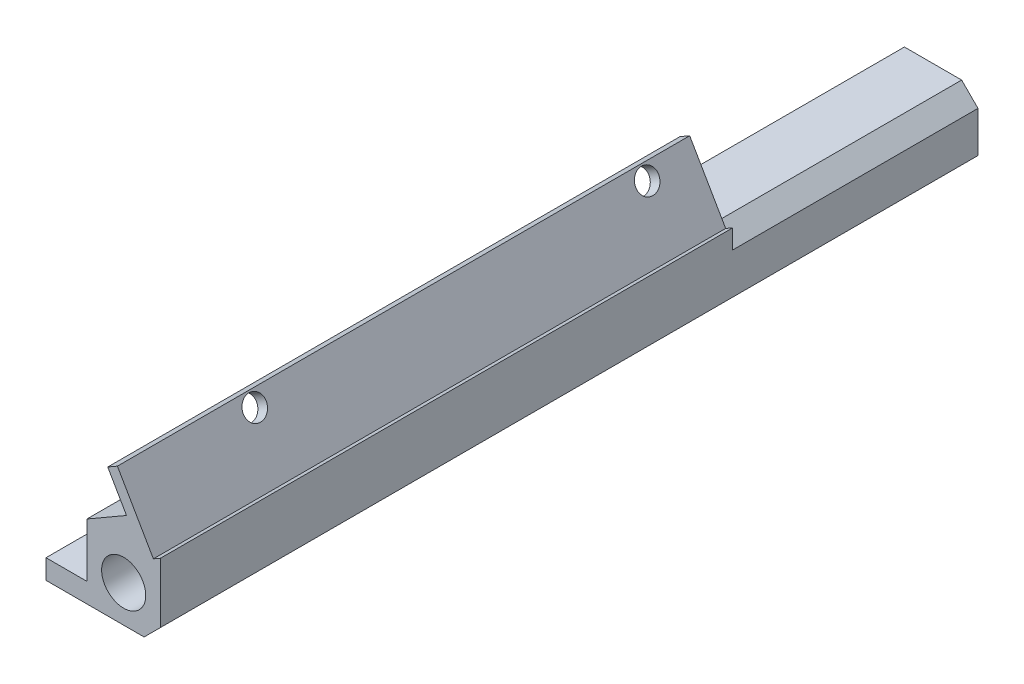
SolidWorks part; units mm, degrees
ref_plane "Front Plane" through (0, 0, 0) normal (0, 0, 1) x (1, 0, 0)
ref_plane "Top Plane" through (0, 0, 0) normal (0, 1, 0) x (1, 0, 0)
ref_plane "Right Plane" through (0, 0, 0) normal (1, 0, 0) x (0, 0, -1)
sketch "Sketch1" plane through (0, 0, 0) normal (0, 1, 0) x (1, 0, 0)
  line L1 (0, 0) -> (77.47, 0)
  line L2 (0, 0) -> (0, 127)
  line L3 (0, 127) -> (77.47, 127)
  line L4 (77.47, 0) -> (77.47, 127)
  dimension "D1" = 77.47
  dimension "D2" = 127
extrude "Boss-Extrude1" add sketch "Sketch1" along normal blind 11.43
sketch "Sketch2" plane through (0, 0, 0) normal (0, 0, 1) x (1, 0, 0)
  line L0 (5.715, 5.715) -> (71.755, 5.715) construction
  line L1 (38.735, 11.43) -> (38.735, 0) construction
  line L2 (0, 11.43) -> (77.47, 11.43) construction
  line L3 (0, 0) -> (77.47, 0) construction
  circle A0 centre (5.715, 5.715) radius 3.429
  circle A1 centre (71.755, 5.715) radius 3.429
  point P10 (38.735, 5.715)
  dimension "D1" = 6.858
  dimension "D2" = 66.04
extrude "Cut-Extrude1" cut sketch "Sketch2" against normal through all
sketch "Sketch3" plane through (0, 11.43, 0) normal (0, 1, 0) x (1, 0, 0)
  line L0 (11.43, 127) -> (11.43, 88.9)
  line L1 (77.47, 127) -> (0, 127) construction
  line L2 (11.43, 127) -> (66.04, 127)
  line L3 (66.04, 127) -> (66.04, 88.9)
  line L4 (53.34, 76.2) -> (24.13, 76.2)
  line L5 (0, 127) -> (0, 0) construction
  arc A0 (66.04, 88.9) -> (53.34, 76.2) centre (53.34, 88.9) cw
  arc A1 (24.13, 76.2) -> (11.43, 88.9) centre (24.13, 88.9) cw
  point P10 (38.735, 127)
  dimension "D1" = 12.7
  dimension "D2" = 11.43
  dimension "D3" = 50.8
extrude "Cut-Extrude2" cut sketch "Sketch3" against normal through all
sketch "Sketch4" plane through (0, 0, -127) normal (0, 0, -1) x (-1, 0, 0)
  line L0 (-11.43, 0) -> (-11.43, 11.43) construction
  line L1 (-66.04, 11.43) -> (-11.43, 11.43)
  line L2 (-66.04, 11.43) -> (-66.04, 5.08)
  line L3 (-66.04, 5.08) -> (-11.43, 5.08)
  line L4 (-11.43, 11.43) -> (-11.43, 5.08)
  line L5 (-11.43, 0) -> (0, 0) construction
  dimension "D1" = 5.08
extrude "Cut-Extrude3" cut sketch "Sketch4" against normal through all
chamfer "Chamfer1" distance 2.54 angle 45 4 edges at (0, 0, -63.5) (0, 11.43, -63.5) (77.47, 0, -63.5) (77.47, 11.43, -63.5)
sketch "Sketch5" plane through (0, 11.43, 0) normal (0, 1, 0) x (1, 0, 0)
  line L0 (66.04, 76.2) -> (0, 76.2)
  line L1 (66.04, 0) -> (66.04, 88.9) construction
  line L2 (0, 0) -> (0, 127) construction
  line L3 (0, 76.2) -> (0, 127)
  line L4 (0, 127) -> (66.04, 127)
  line L5 (66.04, 127) -> (66.04, 76.2)
  line L6 (24.13, 76.2) -> (53.34, 76.2) construction
extrude "Cut-Extrude4" cut sketch "Sketch5" against normal through all
sketch "Sketch6" plane through (0, 11.43, 0) normal (0, 1, 0) x (1, 0, 0)
  line L0 (53.34, 76.2) -> (53.34, 0)
  line L1 (11.43, 76.2) -> (66.04, 76.2) construction
  line L2 (66.04, 0) -> (11.43, 0) construction
  line L3 (53.34, 0) -> (0, 0)
  line L4 (0, 0) -> (0, 76.2)
  line L5 (0, 76.2) -> (53.34, 76.2)
  line L6 (66.04, 0) -> (66.04, 127) construction
  dimension "D1" = 12.7
extrude "Cut-Extrude5" cut sketch "Sketch6" against normal through all
sketch "Sketch7" plane through (0, 5.08, 0) normal (0, 1, 0) x (1, 0, 0)
  line L0 (53.34, 76.2) -> (66.04, 76.2) construction
  line L1 (66.04, 0) -> (66.04, 76.2) construction
  circle A0 centre (62.23, 68.58) radius 1.778
  circle A4 centre (62.23, 7.62) radius 1.778
  dimension "D1" = 3.556
  dimension "D2" = 7.62
  dimension "D3" = 68.58
  dimension "D4" = 3.81
extrude "Hole Cuts 1" cut sketch "Sketch7" against normal through all
sketch "Sketch8" plane through (0, 0, 0) normal (0, 0, 1) x (1, 0, 0)
  line L0 (77.47, 11.8699) -> (77.47, 7.0306)
  line L1 (77.47, 11.8699) -> (71.882, 21.5486)
  line L2 (71.882, 21.5486) -> (68.6183, 19.6643)
  line L3 (68.6183, 19.6643) -> (71.5393, 14.605)
  line L4 (71.5393, 14.605) -> (66.04, 11.43)
  line L5 (77.47, 11.43) -> (68.58, 11.43) construction
  line L6 (66.04, 11.43) -> (74.93, 11.43) construction
  line L7 (66.04, 11.43) -> (74.93, 11.43)
  line L8 (74.93, 11.43) -> (77.47, 7.0306)
  line L9 (77.47, 8.89) -> (77.47, 2.54) construction
  dimension "D2" = 11.176
  dimension "D3" = 6.35
  dimension "D4" = 5.842
  dimension "D6" = 60
extrude "Boss-Extrude2" add sketch "Sketch8" against normal blind 88.9
sketch "Sketch9" plane through (0, 0, 0) normal (0, 0, 1) x (1, 0, 0)
  line L0 (74.93, 0) -> (66.04, 0) construction
  line L1 (53.34, 0) -> (74.93, 0) construction
  line L3 (66.04, 0) -> (59.69, 0) construction
  line L4 (59.69, 0) -> (53.34, 0)
  line L5 (53.34, 0) -> (53.34, 5.08)
  line L6 (53.34, 5.08) -> (59.69, 5.08)
  line L7 (66.04, 5.08) -> (53.34, 5.08) construction
  line L8 (59.69, 5.08) -> (59.69, 0)
  dimension "D1" = 6.35
extrude "Cut-Extrude7" cut sketch "Sketch9" against normal up to next
sketch "Sketch10" plane through (0, 0, 0) normal (0, 0, 1) x (1, 0, 0)
  line L0 (59.69, 5.08) -> (66.04, 5.08)
  line L1 (66.04, 5.08) -> (66.04, 3.81)
  line L2 (66.04, 3.81) -> (59.69, 3.81)
  line L3 (59.69, 0) -> (59.69, 5.08) construction
  line L4 (59.69, 3.81) -> (59.69, 5.08)
  line L5 (59.69, 0) -> (74.93, 0) construction
  dimension "D1" = 3.81
extrude "Cut-Extrude8" cut sketch "Sketch10" against normal up to next
sketch "Sketch11" plane through (59.9786, 34.6287, 0) normal (-0.866, -0.5, 0) x (0, 0, 1)
  line L0 (-88.9, -23.1213) -> (0, -23.1213) construction
  line L1 (-88.9, -17.2793) -> (-88.9, -23.1213) construction
  circle A0 centre (-20.32, -19.3113) radius 1.778
  circle A1 centre (-81.28, -19.3113) radius 1.778
  dimension "D1" = 3.556
  dimension "D2" = 3.81
  dimension "D3" = 7.62
  dimension "D4" = 68.58
extrude "Hole Cuts 2" cut sketch "Sketch11" against normal up to next
sketch "Sketch12" plane through (63.2423, 36.513, 0) normal (0.866, 0.5, 0) x (0, 0, -1)
  line L1 (88.9, -17.2793) -> (0, -17.2793)
  line L2 (88.9, -17.2793) -> (88.9, -28.4553)
  line L3 (88.9, -28.4553) -> (0, -28.4553)
  line L4 (0, -17.2793) -> (0, -28.4553)
extrude "Cut-Extrude10" cut sketch "Sketch12" against normal blind 1.27
sketch "Sketch13" plane through (59.9786, 34.6287, 0) normal (-0.866, -0.5, 0) x (0, 0, 1)
  line L1 (-88.9, -17.2793) -> (0, -17.2793)
  line L2 (-88.9, -17.2793) -> (-88.9, -23.1213)
  line L3 (-88.9, -23.1213) -> (0, -23.1213)
  line L4 (0, -17.2793) -> (0, -23.1213)
extrude "Cut-Extrude11" cut sketch "Sketch13" against normal blind 0.762
sketch "Sketch14" plane through (0, 3.81, 0) normal (0, 1, 0) x (1, 0, 0)
  line L1 (59.69, 76.2) -> (66.04, 76.2)
  line L2 (59.69, 76.2) -> (59.69, 0)
  line L3 (59.69, 0) -> (66.04, 0)
  line L4 (66.04, 76.2) -> (66.04, 0)
extrude "Cut-Extrude12" cut sketch "Sketch14" against normal blind 0.762
